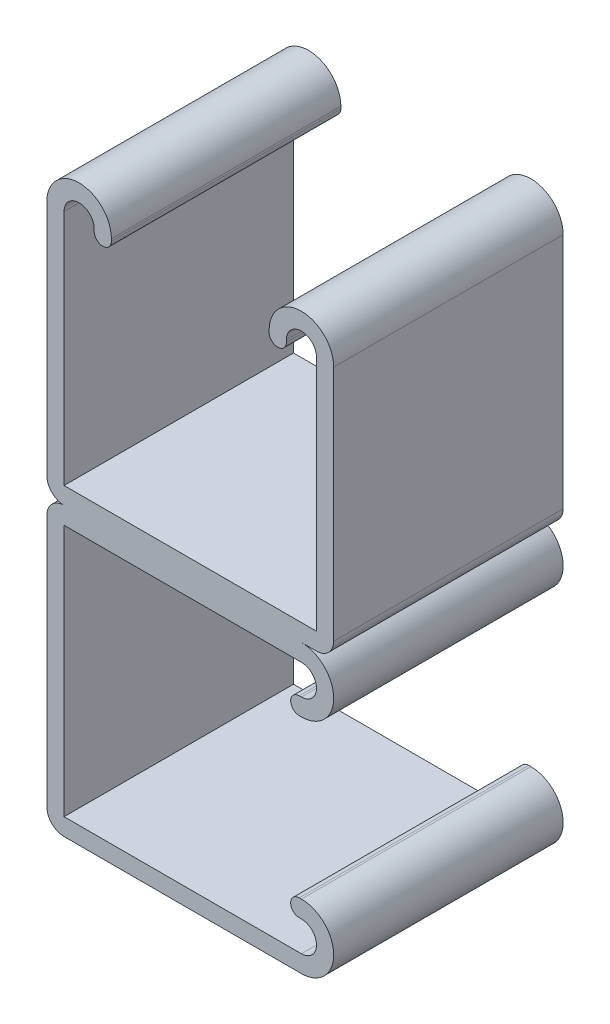
SolidWorks part; units mm, degrees
note: '?' marks a value the reader was unsure of.
ref_plane "Plane1" through (0, 0, 0) normal (0, 0, 1) x (1, 0, 0)
ref_plane "Plane2" through (0, 0, 0) normal (0, 1, 0) x (1, 0, 0)
ref_plane "Plane3" through (0, 0, 0) normal (1, 0, 0) x (0, 0, -1)
sketch "Sketch1" plane through (0, 0, 0) normal (0, 0, 1) x (1, 0, 0)
  line L0 (0, 28.1781) -> (0, 1.905)
  line L1 (1.905, 0) -> (29.845, 0)
  line L2 (31.75, 1.905) -> (31.75, 28.1781)
  line L3 (24.6062, 28.1781) -> (24.6062, 27.94)
  line L4 (7.1438, 28.1781) -> (7.1437, 27.94)
  line L5 (5.2388, 28.1781) -> (5.2387, 27.94)
  line L6 (1.905, 28.1781) -> (1.905, 1.905)
  line L7 (1.905, 1.905) -> (29.845, 1.905)
  line L8 (29.845, 1.905) -> (29.845, 28.1781)
  line L9 (26.5112, 28.1781) -> (26.5113, 27.94)
  line L10 (-4.7625, 31.75) -> (46.0375, 31.75) construction
  line L11 (7.7851, 26.9875) -> (33.4899, 26.9875) construction
  arc A0 (31.75, 28.1781) -> (24.6062, 28.1781) centre (28.1781, 28.1781) ccw
  arc A1 (0, 28.1781) -> (7.1438, 28.1781) centre (3.5719, 28.1781) cw
  arc A2 (1.905, 0) -> (0, 1.905) centre (1.905, 1.905) cw
  arc A3 (29.845, 0) -> (31.75, 1.905) centre (29.845, 1.905) ccw
  arc A4 (1.905, 28.1781) -> (5.2388, 28.1781) centre (3.5719, 28.1781) cw
  arc A5 (29.845, 28.1781) -> (26.5112, 28.1781) centre (28.1781, 28.1781) ccw
  arc A6 (24.6062, 27.94) -> (26.5113, 27.94) centre (25.5587, 27.94) ccw
  arc A7 (7.1437, 27.94) -> (5.2387, 27.94) centre (6.1913, 27.94) cw
  dimension "D6" = 7.1437
  dimension "D7" = 17.4625
  dimension "D9" = 4.7625
  dimension "D2" = 31.75
extrude "Base-Extrude" add sketch "Sketch1" along normal mid plane 25.4
ref_axis "Axis1" through (0, 0, -50) along (0, 0, 1)?
pattern_circular "CirPattern1" count 2 every 270 about axis through (0, 0, 0) along (0, 0, 1) of "Base-Extrude"
equation "\"D7@Sketch1\" = \"Width@Sketch1\" - 2 * \"D6@Sketch1\""
equation "\"D1@Sketch1\" = \"gauge@Sketch1\""
